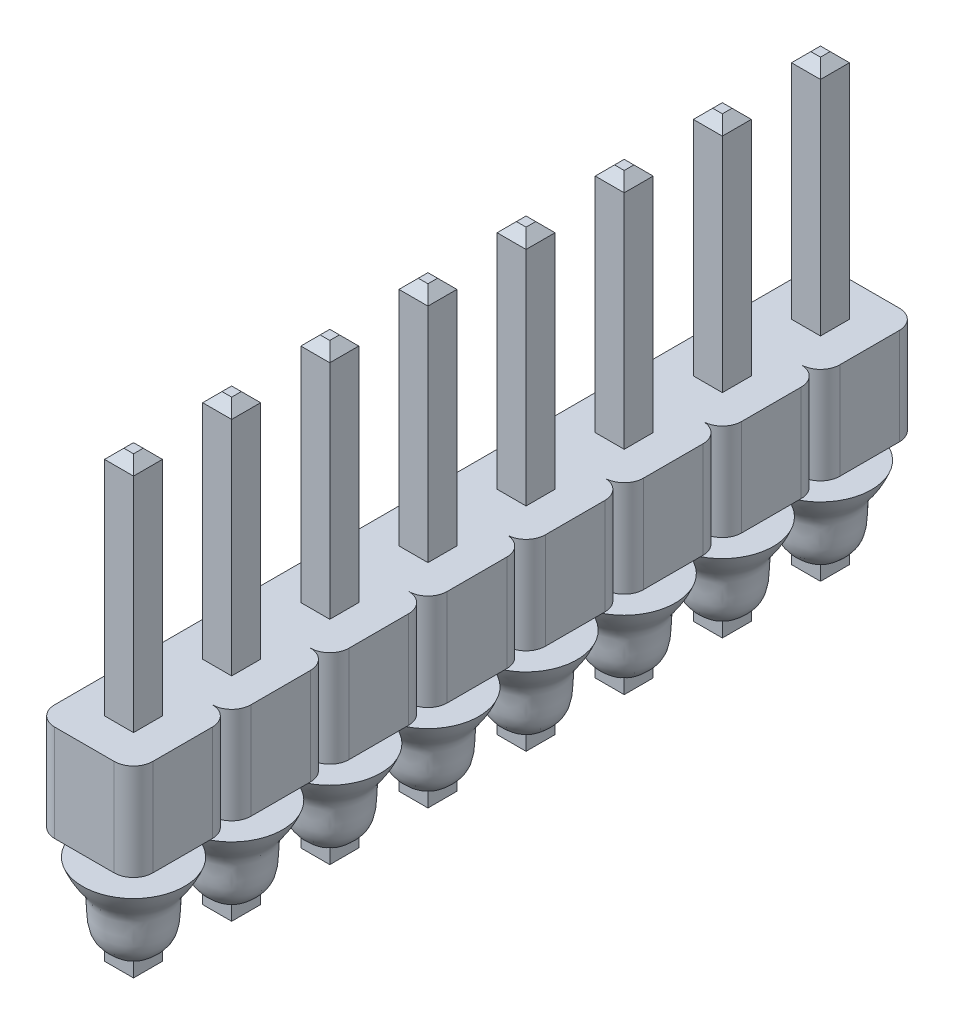
SolidWorks part; units mm, degrees
ref_plane "Front Plane" through (0, 0, 0) normal (0, 0, 1) x (1, 0, 0)
ref_plane "Top Plane" through (0, 0, 0) normal (0, 1, 0) x (1, 0, 0)
ref_plane "Right Plane" through (0, 0, 0) normal (1, 0, 0) x (0, 0, -1)
ref_plane "Plane1" through (0, 0, 0) normal (0, 1, 0) x (-1, 0, 0)
sketch "Sketch1" plane through (0, 0, 0) normal (0, 1, 0) x (-1, 0, 0)
  line L0 (-0.77, 1.27) -> (0.77, 1.27)
  line L1 (1.27, 0.77) -> (1.27, -0.77)
  line L2 (0.77, -1.27) -> (-0.77, -1.27)
  line L3 (-1.27, -0.77) -> (-1.27, 0.77)
  line L4 (-0.77, 0.77) -> (0.77, -0.77) construction
  arc A0 (1.27, 0.77) -> (0.77, 1.27) centre (0.77, 0.77) ccw
  arc A1 (0.77, -1.27) -> (1.27, -0.77) centre (0.77, -0.77) ccw
  arc A2 (-1.27, -0.77) -> (-0.77, -1.27) centre (-0.77, -0.77) ccw
  arc A3 (-0.77, 1.27) -> (-1.27, 0.77) centre (-0.77, 0.77) ccw
  dimension "D3" = 0.5
  dimension "D2" = 2.54
extrude "Boss-Extrude1" add sketch "Sketch1" along normal blind 2.5
ref_plane "Plane2" through (0.77, 0, 1.27) normal (-1, 0, 0) x (0, 0, 1)
ref_plane "Plane3" through (0.77, 0, 1.27) normal (0, -1, 0) x (0, 0, 1)
ref_axis "Axis1" through (0.77, 0, -79.63) along (0, 0, 1)
pattern_linear "LPattern1" count 8 spacing 2.54 along (0, 0, 1) of "Boss-Extrude1"
ref_plane "Plane4" through (0, 0, 0) normal (0, 1, 0) x (-1, 0, 0)
sketch "Sketch2" plane through (0, 0, 0) normal (0, 1, 0) x (-1, 0, 0)
  line L0 (-0.375, 0.375) -> (0.375, 0.375)
  line L1 (0.375, 0.375) -> (0.375, -0.375)
  line L2 (0.375, -0.375) -> (-0.375, -0.375)
  line L3 (-0.375, -0.375) -> (-0.375, 0.375)
  line L4 (-0.375, 0.375) -> (0.375, -0.375) construction
  dimension "D1" = 0.75
extrude "Boss-Extrude2" add sketch "Sketch2" along normal blind 8.5 and the other way blind 3.25
ref_plane "Plane5" through (0.3725, 0, 0.3725) normal (-1, 0, 0) x (0, 0, 1)
ref_plane "Plane6" through (0.3725, 0, 0.3725) normal (0, -1, 0) x (0, 0, 1)
ref_axis "Axis2" through (0.3725, 0, -80.5275) along (0, 0, 1)
chamfer "Chamfer1" distance 0.25 angle 45 8 edges at (0, -3.25, 0.375) (-0.375, -3.25, 0) (0.375, -3.25, 0) (0, -3.25, -0.375) (0, 8.5, 0.375) (-0.375, 8.5, 0) (0, 8.5, -0.375) (0.375, 8.5, 0)
pattern_linear "LPattern2" count 8 spacing 2.54 along (0, 0, 1) of "Boss-Extrude2", "Chamfer1"
ref_axis "Axis3" through (0, -3.575, 0) along (0, 1, 0)
ref_plane "Plano1" through (0, 0, 0) normal (0, 0, -1) x (-1, 0, 0)
sketch "Esboço1" plane through (0, 0, 0) normal (0, 0, -1) x (-1, 0, 0)
  line L0 (0, -3.2042) -> (0, 0) construction
  line L5 (-1.3202, -0.6613) -> (0, -0.6613)
  line L7 (0, -2.9798) -> (0, -0.6613)
  spline S0 degree 3 poles (0, -2.9798) (-0.6673, -2.5836) (-0.8261, -2.2726) (-0.856, -2.0033) (-0.8769, -1.1891) (-1.1033, -1.2191) (-1.3202, -0.6613) knots 0 0 0 0 0.387504 0.628703 0.689952 1 1 1 1
  dimension "D1" = 2.3185
  dimension "D2" = 0.6613
revolve "Revolução2" add sketch "Esboço1" angle 360 about L0
pattern_linear "Padrão linear1" count 8 spacing 2.54 along (0, 0, 1) of "Revolução2"
